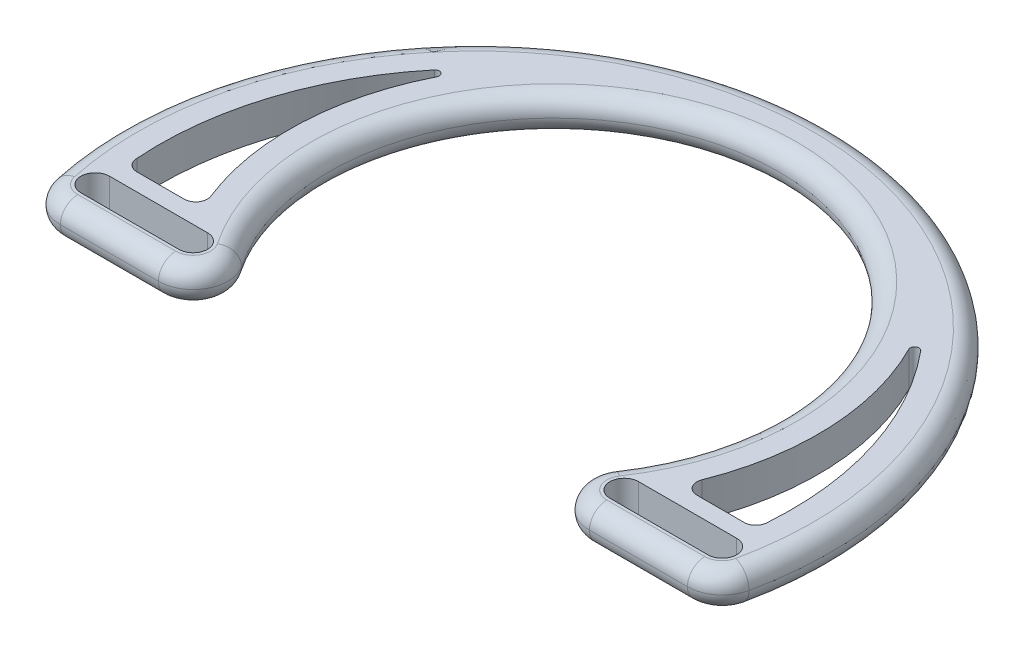
SolidWorks part; units mm, degrees
ref_plane "前视基准面" through (0, 0, 0) normal (0, 0, 1) x (1, 0, 0)
ref_plane "上视基准面" through (0, 0, 0) normal (0, 1, 0) x (1, 0, 0)
ref_plane "右视基准面" through (0, 0, 0) normal (1, 0, 0) x (0, 0, -1)
sketch "草图2" plane through (0, 0, 0) normal (0, 1, 0) x (1, 0, 0)
  line L2 (-36, 0) -> (-24.75, 0) construction
  line L3 (-36, 1.65) -> (-24.75, 1.65)
  line L4 (-36, -1.65) -> (-24.75, -1.65)
  line L7 (-24.75, -4) -> (-36, -4)
  line L8 (0, 48.4771) -> (0, 42.5093) construction
  line L9 (36, 0) -> (24.75, 0) construction
  line L10 (36, 1.65) -> (24.75, 1.65)
  line L11 (36, -1.65) -> (24.75, -1.65)
  line L12 (24.75, -4) -> (36, -4)
  arc A0 (-21.4323, 2.2345) -> (21.4323, 2.2345) centre (0, 16.6693) cw
  circle A1 centre (0, 16.6693) radius 25.84 construction
  circle A3 centre (0, 7.6693) radius 40.8079 construction
  arc A5 (-36, 1.65) -> (-36, -1.65) centre (-36, 0) ccw
  arc A6 (-24.75, -1.65) -> (-24.75, 1.65) centre (-24.75, 0) ccw
  arc A7 (-21.4323, 2.2345) -> (-24.75, -4) centre (-24.75, 0) cw
  arc A8 (-36, -4) -> (-39.9122, -0.8334) centre (-36, 0) cw
  arc A9 (-39.9122, -0.8334) -> (39.9122, -0.8334) centre (0, 7.6693) cw
  arc A10 (36, 1.65) -> (36, -1.65) centre (36, 0) cw
  arc A11 (24.75, -1.65) -> (24.75, 1.65) centre (24.75, 0) cw
  arc A12 (36, -4) -> (39.9122, -0.8334) centre (36, 0) ccw
  arc A13 (21.4323, 2.2345) -> (24.75, -4) centre (24.75, 0) ccw
  point P18 (-30.375, 0)
  point P36 (30.375, 0)
  dimension "D1" = 1.65
  dimension "D2" = 9
extrude "凸台-拉伸1" add sketch "草图2" along normal blind 4
fillet "圆角1" radius 2 16 edges at (-38.5166, 0, 3.1092) (0, 0, -48.4771) (38.5166, 0, 3.1092) (30.375, 0, 4) (21.2189, 0, 1.8791) (0, 0, -42.5093) (-21.2189, 0, 1.8791) (-21.2189, 4, 1.8791) (-30.375, 4, 4) (-38.5166, 4, 3.1092) (0, 4, -48.4771) (38.5166, 4, 3.1092) (30.375, 4, 4) (21.2189, 4, 1.8791) (-30.375, 0, 4) (0, 4, -42.5093)
sketch "草图3" plane through (0, 4, 0) normal (0, 1, 0) x (1, 0, 0)
  line L0 (-34.8722, 4.9823) -> (-29.4373, 4.9823) construction
  line L1 (-34.8722, 6.3147) -> (-29.4373, 6.3147)
  line L2 (-34.8722, 3.65) -> (-29.4373, 3.65)
  line L3 (-24.75, 1.65) -> (-36, 1.65) construction
  arc A0 (23.0912, 1.1172) -> (-23.0912, 1.1172) centre (0, 16.6693) ccw construction
  arc A1 (37.9561, -0.4167) -> (-37.9561, -0.4167) centre (0, 7.6693) ccw construction
  arc A2 (-34.8722, 6.3147) -> (-34.8722, 3.65) centre (-34.8722, 4.9823) ccw
  arc A3 (-29.4373, 3.65) -> (-29.4373, 6.3147) centre (-29.4373, 4.9823) ccw
  arc A8 (23.0912, 1.1172) -> (-23.0912, 1.1172) centre (0, 16.6693) ccw construction
  arc A9 (37.9561, -0.4167) -> (-37.9561, -0.4167) centre (0, 7.6693) ccw construction
  circle A10 centre (0, 16.6693) radius 30.34
  circle A11 centre (0, 7.6693) radius 36.3079
  point P10 (-32.1547, 4.9823)
  dimension "D1" = 2.5
  dimension "D2" = 2.5
  dimension "D3" = 2
sketch "草图4" plane through (0, 4, 0) normal (0, 1, 0) x (1, 0, 0)
  line L0 (-34.8722, 3.65) -> (-29.4373, 3.65) construction
  line L1 (-34.8722, 3.65) -> (-29.4373, 3.65)
  arc A0 (-28.199, 5.474) -> (-27.094, 30.3233) centre (0, 16.6693) cw
  arc A1 (-29.4373, 3.65) -> (-29.4373, 6.3147) centre (-29.4373, 4.9823) ccw construction
  arc A3 (-36.2045, 4.9823) -> (-27.9251, 30.8678) centre (0, 7.6693) cw
  arc A4 (-34.8722, 6.3147) -> (-34.8722, 3.65) centre (-34.8722, 4.9823) ccw construction
  arc A6 (-36.2045, 4.9823) -> (-34.8722, 3.65) centre (-34.8722, 4.9823) ccw
  arc A7 (-28.199, 5.474) -> (-29.4373, 3.65) centre (-29.4373, 4.9823) cw
  arc A8 (-27.094, 30.3233) -> (-27.9251, 30.8678) centre (-27.5405, 30.5483) ccw
  circle A9 centre (0, 16.6693) radius 30.34 construction
  dimension "D1" = 0.5
extrude "切除-拉伸2" cut sketch "草图4" against normal through all
mirror "镜向1" about plane through (0, 0, 0) normal (1, 0, 0) of "切除-拉伸2"
